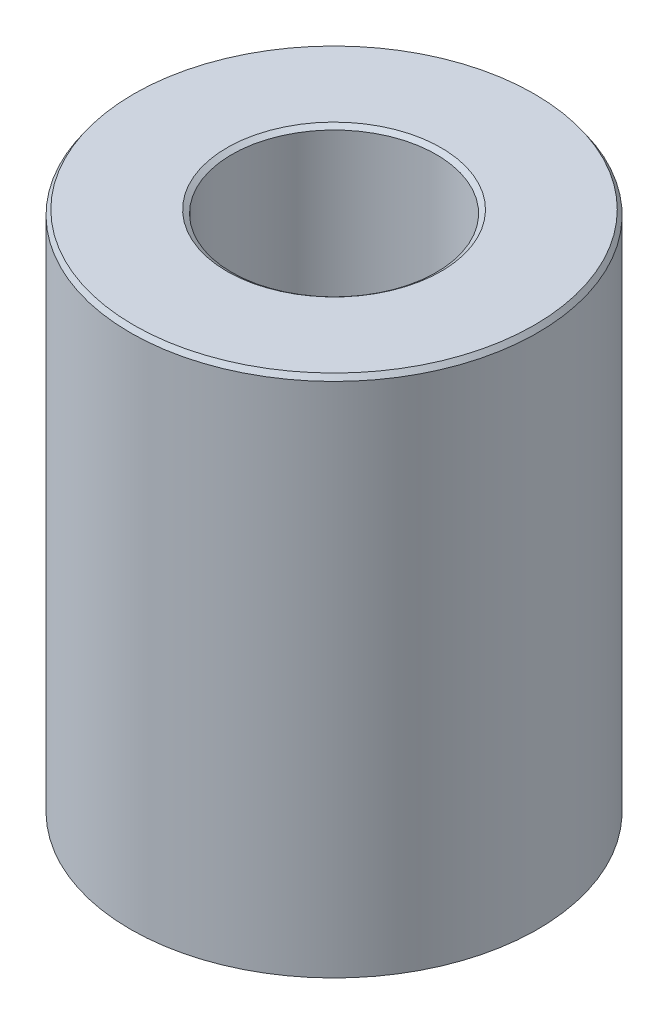
SolidWorks part; units mm, degrees
ref_plane "Front Plane" through (0, 0, 0) normal (0, 0, 1) x (1, 0, 0)
ref_plane "Top Plane" through (0, 0, 0) normal (0, 1, 0) x (1, 0, 0)
ref_plane "Right Plane" through (0, 0, 0) normal (1, 0, 0) x (0, 0, -1)
sketch "Sketch1" plane through (0, 0, 0) normal (0, 1, 0) x (1, 0, 0)
  circle A0 centre (0, 0) radius 42.5
  dimension "SLEEVE_OD" = 85
extrude "Boss-Extrude1" add sketch "Sketch1" along normal blind 109.5249
sketch "Sketch2" plane through (0, 0, 0) normal (0, 1, 0) x (1, 0, 0)
  circle A0 centre (0, 0) radius 21.3304
  dimension "BORE_D" = 42.6608
extrude "Cut-Extrude1" cut sketch "Sketch2" along normal through all
chamfer "Chamfer1" distance 1.0163 angle 34.878 4 edges at (0, 109.5249, 21.3304) (0, 0, 21.3304) (0, 0, 42.5) (0, 109.5249, 42.5) first distance on face at (0, 109.5249, 21.3304) first distance on face at (0, 0, 21.3304) first distance on face at (0, 109.5249, 42.5)
